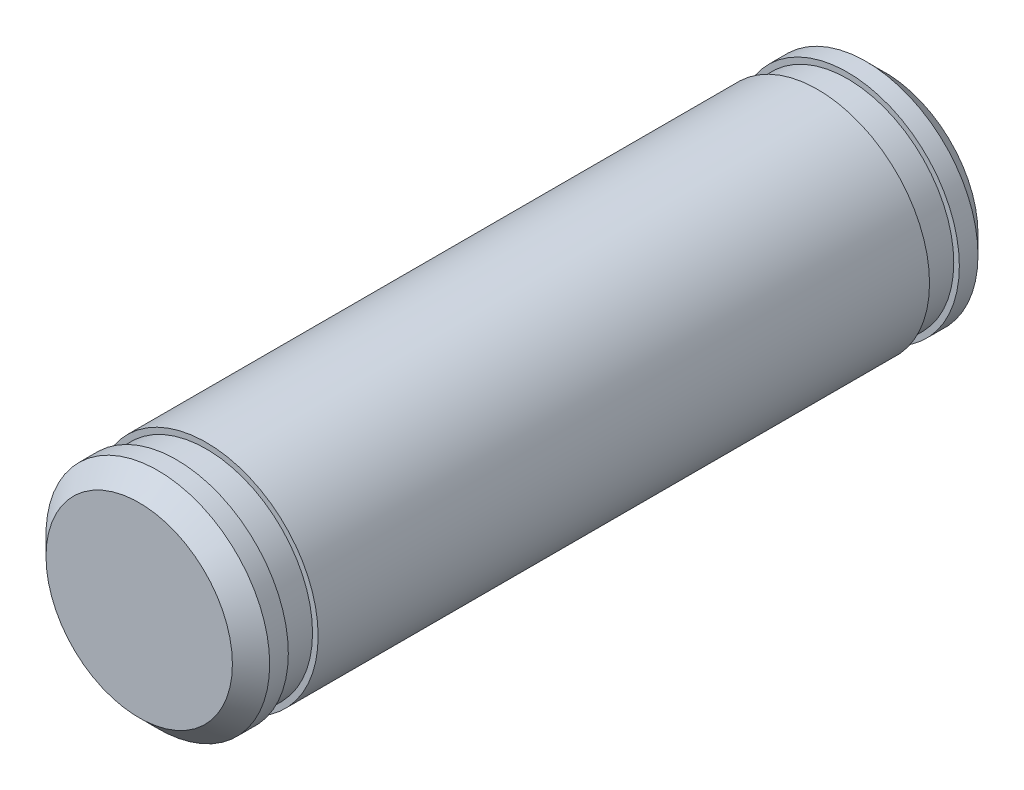
SolidWorks part; units mm, degrees
material "Stop 1060"
ref_plane "Płaszczyzna przednia" through (0, 0, 0) normal (0, 0, 1) x (1, 0, 0)
ref_plane "Płaszczyzna górna" through (0, 0, 0) normal (0, 1, 0) x (1, 0, 0)
ref_plane "Płaszczyzna prawa" through (0, 0, 0) normal (1, 0, 0) x (0, 0, -1)
sketch "Szkic1" plane through (0, 0, 0) normal (0, 0, 1) x (1, 0, 0)
  circle A0 centre (0, 0) radius 3
  dimension "D1" = 6
extrude "Dodanie-wyciągnięcie1" add sketch "Szkic1" along normal blind 20
sketch "Szkic2" plane through (0, 0, 20) normal (0, 0, 1) x (1, 0, 0)
  circle A0 centre (0, 0) radius 3
  circle A1 centre (0, 0) radius 2.85
  dimension "D1" = 6
  dimension "D2" = 5.7
extrude "Wytnij-wyciągnięcie1" cut sketch "Szkic2" against normal blind 0.8 from offset 1 offset against normal yes
extrude "Wytnij-wyciągnięcie2" cut sketch "Szkic2<2>" along normal blind 0.8 from offset 19 offset against normal yes
sketch "Szkic2<2>" plane through (0, 0, 20) normal (0, 0, 1) x (1, 0, 0) same geometry as "Szkic2"
chamfer "Sfazowanie1" distance 0.5 angle 45 2 edges at (3, 0, 0) (3, 0, 20)
